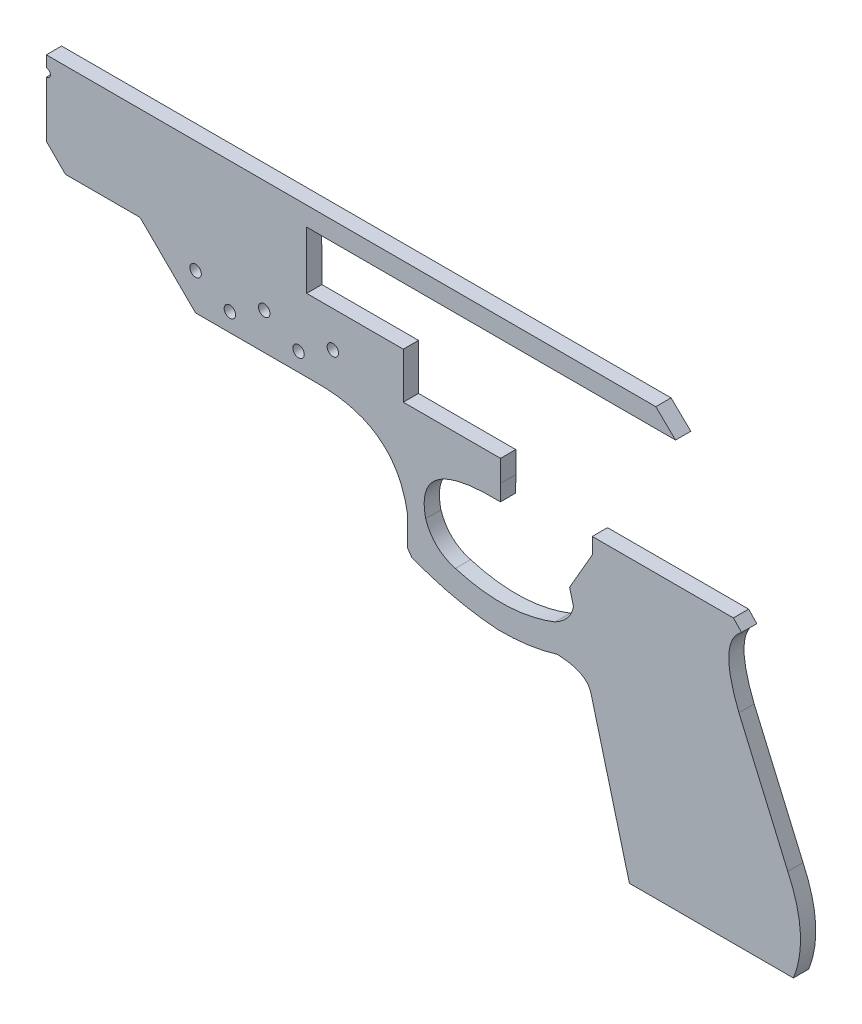
SolidWorks part; units mm, degrees
ref_plane "Front Plane" through (0, 0, 0) normal (0, 0, 1) x (1, 0, 0)
ref_plane "Top Plane" through (0, 0, 0) normal (0, 1, 0) x (1, 0, 0)
ref_plane "Right Plane" through (0, 0, 0) normal (1, 0, 0) x (0, 0, -1)
sketch "Sketch1" plane through (0, 0, 0) normal (0, 0, 1) x (1, 0, 0)
  line L0 (275.2156, 1168.292) -> (1376.0774, 1168.292) construction
  line L1 (2306.6441, 819.9826) -> (1936.601, 819.9826)
  line L2 (504.9927, 1197.919) -> (2103.2357, 1197.9722)
  line L3 (2103.2357, 1197.9722) -> (2154.992, 1147.9826)
  line L4 (750.7862, 951.5045) -> (554.9909, 951.506)
  line L5 (2306.6441, 819.9826) -> (2328.1936, 797.6651)
  line L6 (1441.0732, 997.4486) -> (1187.5655, 997.4486)
  line L7 (2286.5164, 840.8277) -> (2328.1936, 797.6651) construction
  line L8 (1186.9916, 1147.9826) -> (1187.5655, 997.4486)
  line L9 (1696.0732, 819.9826) -> (1696.0732, 877.0374)
  line L10 (1790.0732, 877.0374) -> (1535.0732, 877.0374) construction
  line L11 (2321.1197, 611.9262) -> (2449.3622, 315.5346)
  line L12 (2463.9434, 80.874) -> (2033.9434, 80.8955)
  line L13 (2033.9434, 80.8955) -> (1933.2319, 462.1503)
  line L14 (1695.7737, 777.9656) -> (1695.2927, 777.9826)
  line L15 (1441.0732, 877.0374) -> (1441.0732, 997.4486)
  line L16 (1696.0732, 877.0374) -> (1441.0732, 877.0374)
  line L17 (554.9909, 951.506) -> (504.9913, 1001.5063)
  line L19 (1936.601, 819.9826) -> (1936.601, 777.9826)
  line L20 (1936.601, 777.9826) -> (1877.0493, 674.8361)
  line L21 (2154.992, 1147.9826) -> (1186.9916, 1147.9826)
  line L23 (750.7862, 951.5045) -> (896.3629, 807.3806)
  line L24 (1214.0944, 807.3806) -> (896.3629, 807.3806)
  line L26 (1696.0732, 819.9826) -> (1695.7737, 777.9656)
  line L27 (504.9913, 1001.5063) -> (504.9925, 1147.2379)
  line L29 (1463.3169, 535.642) -> (1452.3791, 551.1255)
  line L30 (1452.3791, 551.1255) -> (1452.3791, 627.629)
  line L31 (1887.2046, 636.3922) -> (1877.0493, 674.8361)
  line L32 (504.9927, 1197.919) -> (504.9925, 1168.6)
  arc A0 (504.9925, 1168.6) -> (504.9925, 1147.2379) centre (504.9924, 1157.919) cw
  circle A1 centre (896.3629, 903.3806) radius 15
  circle A2 centre (986.3629, 855.3806) radius 15
  circle A3 centre (1076.3629, 903.3806) radius 15
  circle A4 centre (1166.3629, 855.3806) radius 15
  circle A5 centre (1256.3629, 903.3806) radius 15
  spline S0 degree 2 poles (1839.0283, 577.045) (1881.4356, 600.2191) (1887.2046, 636.3922) knots 0 0 0 0.760506 0.760506 0.760506
  spline S1 degree 2 poles (2449.3622, 315.5346) (2507.6289, 190.0982) (2463.9434, 80.874) knots 0 0 0 1 1 1
  spline S2 degree 2 poles (2321.1197, 611.9262) (2264.6079, 751.553) (2328.1936, 797.6651) knots 0 0 0 0.701234 0.701234 0.701234
  spline S3 degree 3 poles (1844.4882, 506.2174) (1896.9871, 504.8056) (1926.7795, 489.3172) (1933.8654, 459.7523) knots 0 0 0 0 0.746569 0.746569 0.746569 0.746569
  spline S4 degree 2 poles (1452.3791, 627.629) (1422.4271, 809.111) (1214.0944, 807.3806) knots 0 0 0 0.82397 0.82397 0.82397
  spline S5 degree 2 poles (1463.3169, 535.642) (1573.7016, 492.3812) (1689.3732, 484.6641) knots 0 0 0 1 1 1
  spline S6 degree 2 poles (1689.3732, 484.6641) (1769.5231, 483.4624) (1844.4882, 506.2174) knots 0 0 0 1 1 1
  spline S8 degree 2 poles (1695.2927, 777.9826) (1468.3908, 784.5404) (1499.6836, 641.8152) knots 0 0 0 1 1 1
  spline S9 degree 2 poles (1499.6836, 641.8152) (1519.6534, 584.0683) (1577.5301, 567.9309) knots 0 0 0 1 1 1
  spline S10 degree 2 poles (1577.5301, 567.9309) (1712.5573, 527.6653) (1839.0283, 577.045) knots 0 0 0 1 1 1
extrude "Boss-Extrude1" add sketch "Sketch1" along normal blind 40 contours S10 S9 S8 L14 L26 L9 L16 L15 L6 L8 L21 L3 L2 L32 A0 L27 L17 L4 L23 L24 S4 L30 L29 S5 S6 S3 L13 L12 S1 L11 S2 L5 L1 L19 L20 L31 S0 A1 A2 A3 A4 A5 | S3 S6 S5 L29 L30 S4 L24 L23 L4 L17 L27 A0 L32 L2 L3 L21 L8 L6 L15 L16 L9 L26 L14 S8 S9 S10 S0 L31 L20 L19 L1 L5 S2 L11 S1 L12 L13 region at (2301.0792, 793.0465, 0)
